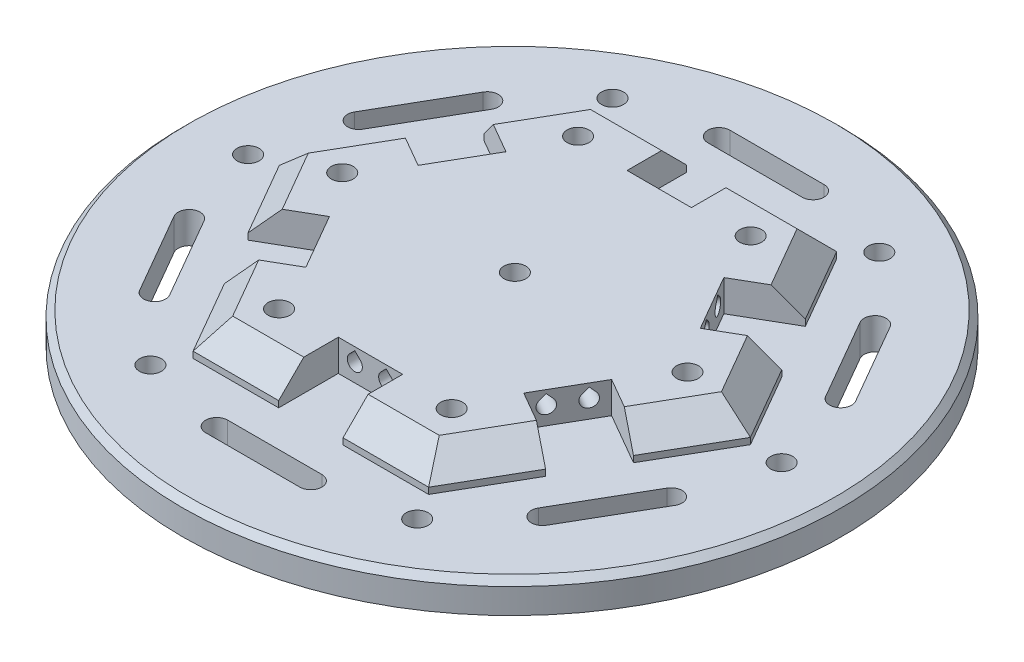
SolidWorks part; units mm, degrees
ref_plane "前基準面" through (0, 0, 0) normal (0, 0, 1) x (1, 0, 0)
ref_plane "上基準面" through (0, 0, 0) normal (0, 1, 0) x (1, 0, 0)
ref_plane "右基準面" through (0, 0, 0) normal (1, 0, 0) x (0, 0, -1)
sketch "草圖1" plane through (0, 0, 0) normal (0, 1, 0) x (1, 0, 0)
  line L0 (0, -1000) -> (0, 49000) construction
  line L1 (75.0555, 0) -> (37.5278, 65)
  line L2 (37.5278, 65) -> (-37.5278, 65)
  line L3 (-37.5278, 65) -> (-75.0555, 0)
  line L4 (-75.0555, 0) -> (-37.5278, -65)
  line L5 (-37.5278, -65) -> (37.5278, -65)
  line L6 (37.5278, -65) -> (75.0555, 0)
  line L7 (-10.25, 49) -> (10.25, 49)
  line L8 (-10.25, 49) -> (-10.25, 46)
  line L9 (-10.25, 46) -> (10.25, 46)
  line L10 (10.25, 49) -> (10.25, 46)
  line L11 (37.3102, 33.3768) -> (34.7122, 31.8768)
  line L12 (-10.25, 46) -> (10.25, 46) construction
  line L13 (-10.25, 46) -> (-10.25, 18) construction
  line L14 (-10.25, 18) -> (10.25, 18) construction
  line L15 (10.25, 46) -> (10.25, 18) construction
  line L16 (37.3102, 33.3768) -> (47.5602, 15.6232)
  line L17 (47.5602, 15.6232) -> (44.9622, 14.1232)
  line L18 (34.7122, 31.8768) -> (44.9622, 14.1232)
  line L19 (44.9622, 14.1232) -> (20.7135, 0.1232) construction
  line L20 (10.4635, 17.8768) -> (20.7135, 0.1232) construction
  line L21 (34.7122, 31.8768) -> (10.4635, 17.8768) construction
  line L22 (47.5602, -15.6232) -> (44.9622, -14.1232)
  line L23 (47.5602, -15.6232) -> (37.3102, -33.3768)
  line L24 (37.3102, -33.3768) -> (34.7122, -31.8768)
  line L25 (44.9622, -14.1232) -> (34.7122, -31.8768)
  line L26 (34.7122, -31.8768) -> (10.4635, -17.8768) construction
  line L27 (20.7135, -0.1232) -> (10.4635, -17.8768) construction
  line L28 (44.9622, -14.1232) -> (20.7135, -0.1232) construction
  line L29 (10.25, -49) -> (10.25, -46)
  line L30 (10.25, -49) -> (-10.25, -49)
  line L31 (-10.25, -49) -> (-10.25, -46)
  line L32 (10.25, -46) -> (-10.25, -46)
  line L33 (-10.25, -46) -> (-10.25, -18) construction
  line L34 (10.25, -18) -> (-10.25, -18) construction
  line L35 (10.25, -46) -> (10.25, -18) construction
  line L36 (-37.3102, -33.3768) -> (-34.7122, -31.8768)
  line L37 (-37.3102, -33.3768) -> (-47.5602, -15.6232)
  line L38 (-47.5602, -15.6232) -> (-44.9622, -14.1232)
  line L39 (-34.7122, -31.8768) -> (-44.9622, -14.1232)
  line L40 (-44.9622, -14.1232) -> (-20.7135, -0.1232) construction
  line L41 (-10.4635, -17.8768) -> (-20.7135, -0.1232) construction
  line L42 (-34.7122, -31.8768) -> (-10.4635, -17.8768) construction
  line L43 (-47.5602, 15.6232) -> (-44.9622, 14.1232)
  line L44 (-47.5602, 15.6232) -> (-37.3102, 33.3768)
  line L45 (-37.3102, 33.3768) -> (-34.7122, 31.8768)
  line L46 (-44.9622, 14.1232) -> (-34.7122, 31.8768)
  line L47 (-34.7122, 31.8768) -> (-10.4635, 17.8768) construction
  line L48 (-20.7135, 0.1232) -> (-10.4635, 17.8768) construction
  line L49 (-44.9622, 14.1232) -> (-20.7135, 0.1232) construction
  line L51 (10.25, 46) -> (-10.25, 46)
  line L52 (10.25, 46) -> (10.25, 65)
  line L53 (10.25, 65) -> (-10.25, 65)
  line L54 (-10.25, 46) -> (-10.25, 65)
  circle A0 centre (0, 0) radius 65 construction
  circle A2 centre (0, 0) radius 46 construction
  point P14 (0, 46)
  point P51 (0, 0)
  dimension "D1" = 130
  dimension "D2" = 16
  dimension "D3" = 20.5
  dimension "D4" = 3
  dimension "D5" = 28
  dimension "D6" = 6
extrude "填料-伸長1" add sketch "草圖1" along normal blind 10 contours L8 L54 L2 L3 L4 L5 L6 L1 L52 L10 L9 L46 L43 L44 L45 L39 L36 L37 L38 L32 L29 L30 L31 L25 L22 L23 L24 L18 L11 L16 L17 | L54 L7 L52 L2 | L11 L18 L17 L16 | L22 L25 L24 L23 | L36 L39 L38 L37 | L43 L46 L45 L44 | L10 L7 L8 L9 | L29 L32 L31 L30 region at (0, 0, 1.3413) region at (0, 0, -57) region at (0, 0, -47.5) region at (41.1362, 0, -23.75) region at (41.1362, 0, 23.75) region at (0, 0, 47.5) region at (-41.1362, 0, 23.75) region at (-41.1362, 0, -23.75)
chamfer "導角1" distance 8 angle 45 6 edges at (56.2917, 10, 32.5) (0, 10, 65) (-56.2917, 10, 32.5) (-56.2917, 10, -32.5) (0, 10, -65) (56.2917, 10, -32.5)
extrude "除料-伸長2" cut sketch "草圖1<3>" along normal blind 10 contours L54 L7 L52 L2 | L10 L7 L8 L9 region at (0, 0, -57) region at (0, 0, -47.5)
sketch "草圖1<3>" plane through (0, 0, 0) normal (0, 1, 0) x (1, 0, 0) same geometry as "草圖1"
ref_axis "基準軸1" through (0, 10.5, 0) along (0, -1, 0)
sketch "草圖2" plane through (0, 0, -46) normal (0, 0, -1) x (-1, 0, 0)
  line L0 (10.25, 10) -> (-10.25, 10) construction
  line L2 (-5, 5.5) -> (5, 5.5) construction
  line L3 (0, 10.5) -> (0, -0.5) construction
  line L4 (5, -994.5) -> (5, 49005.5) construction
  line L5 (-5, -994.5) -> (-5, 49005.5) construction
  line L6 (-6.6971, 7.1971) -> (-5, 8.8941)
  line L7 (-5, 8.8941) -> (-3.3029, 7.1971)
  line L8 (3.3029, 7.1971) -> (5, 8.8941)
  line L9 (5, 8.8941) -> (6.6971, 7.1971)
  arc A0 (-6.6971, 7.1971) -> (-3.3029, 7.1971) centre (-5, 5.5) ccw
  arc A1 (3.3029, 7.1971) -> (6.6971, 7.1971) centre (5, 5.5) ccw
  point P6 (0, 5.5)
  dimension "D1" = 4.8
  dimension "D2" = 4.8
  dimension "D3" = 4.5
  dimension "D4" = 4.5
  dimension "D5" = 10
  dimension "D6" = 90
  dimension "D7" = 90
extrude "除料-伸長3" cut sketch "草圖2" against normal blind 8.5
sketch "草圖6" plane through (0, 10, 0) normal (0, 1, 0) x (1, 0, 0)
  line L0 (-15.25, 61) -> (-10.25, 54.3333)
  line L2 (-10.25, 46) -> (-10.25, 18)
  line L3 (-10.25, 18) -> (10.25, 18)
  line L4 (10.25, 18.6667) -> (10.25, 18)
  line L5 (15.25, 20.3333) -> (15.25, 13)
  line L6 (-15.25, 13) -> (15.25, 13)
  line L7 (-15.25, 61) -> (-15.25, 13)
  line L8 (-10.25, 46) -> (-10.25, 54.3333)
  line L9 (-10.25, 46) -> (-10.25, 57) construction
  line L10 (10.25, 18.6667) -> (-3.3654, 45.1538)
  line L13 (-3.3654, 45.1538) -> (15.25, 20.3333)
  line L14 (-10.25, 46) -> (10.25, 18.6667) construction
  line L15 (-15.25, 61) -> (15.25, 20.3333) construction
  dimension "D1" = 28
  dimension "D2" = 20.5
  dimension "D3" = 5
extrude "填料-伸長2" [suppressed] add sketch "草圖6" along normal blind 10
pattern_circular "環狀複製排列1" count 6 over 360 about axis through (0, 10.5, 0) along (0, -1, 0) of "除料-伸長2", "除料-伸長3"
sketch "草圖11" plane through (0, 10, 0) normal (0, 1, 0) x (1, 0, 0)
  line L0 (-61.4167, 23.6232) -> (-75.0555, 0) construction
  line L1 (-68.2361, 11.8116) -> (-98.2361, 11.8116)
  line L2 (-68.2361, 11.8116) -> (-68.2361, -11.8116)
  line L3 (-68.2361, -11.8116) -> (-98.2361, -11.8116)
  line L4 (-98.2361, 11.8116) -> (-98.2361, -11.8116)
  line L5 (-75.0555, 0) -> (-61.4167, -23.6232) construction
  circle A0 centre (0, 0) radius 100
  point P9 (0, 0)
  dimension "D2" = 200
  dimension "D1" = 30
extrude "填料-伸長4" [suppressed] add sketch "草圖11" against normal blind 10 contours L2 L1 L4 L3
fillet "圓角1" [suppressed] radius 10
sketch "草圖9" plane through (0, 0, 0) normal (0, -1, 0) x (1, 0, 0)
  circle A0 centre (0, 0.9115) radius 105
  dimension "D1" = 210
extrude "填料-伸長3" add sketch "草圖9" along normal blind 10
sketch "草圖7" plane through (0, 10, 0) normal (0, 1, 0) x (1, 0, 0)
  circle A0 centre (0, 0) radius 3.5
  dimension "D1" = 7
extrude "除料-伸長4" cut sketch "草圖7" against normal through all
sketch "草圖10" plane through (0, 0, 0) normal (0, 1, 0) x (1, 0, 0)
  line L0 (-15, 80) -> (15, 80) construction
  line L1 (-15, 83.5) -> (15, 83.5)
  line L2 (-15, 76.5) -> (15, 76.5)
  arc A1 (-15, 83.5) -> (-15, 76.5) centre (-15, 80) ccw
  arc A2 (15, 76.5) -> (15, 83.5) centre (15, 80) ccw
  point P2 (0, 80)
  point P8 (0, 0)
  dimension "D1" = 7
  dimension "D2" = 30
  dimension "D3" = 80
extrude "除料-伸長5" cut sketch "草圖10" against normal through all
pattern_circular "環狀複製排列2" count 6 over 360 about axis through (0, 10.5, 0) along (0, -1, 0) of "除料-伸長5"
chamfer "導角2" distance 2 angle 45 1 edges at (0, 0, -104.0885)
sketch "草圖13" plane through (0, 10, 0) normal (0, 1, 0) x (1, 0, 0)
  line L0 (0, 0) -> (52.1048, 90.2482)
  line L1 (0, 0) -> (104.996, 0)
  circle A0 centre (27.5, 47.6314) radius 3.5
  circle A1 centre (0, -0.9115) radius 105 construction
  circle A2 centre (42.5, 73.6122) radius 3.5
  dimension "D3" = 7
  dimension "D4" = 7
  dimension "D1" = 55
  dimension "D2" = 60
  dimension "D5" = 85
extrude "除料-伸長6" cut sketch "草圖13" against normal through all contours A0 | A2
pattern_circular "環狀複製排列3" count 6 over 360 about axis through (0, 10.5, 0) along (0, -1, 0) of "除料-伸長6"
sketch "草圖15" plane through (0, -10, 0) normal (0, -1, 0) x (1, 0, 0)
  line L0 (-32.695, -40.6585) -> (26.7489, -40.6585) construction
  text T0 "D" font "CommercialScript BT" height 30
  point P3 (146.3308, -38.25)
  point P4 (118.2199, -39.2841)
  point P5 (105.6135, -38.7045)
  point P6 (101.4114, -39.2841)
  point P7 (95.9051, -39.5739)
  point P8 (-62.996, -23.4876)
  point P9 (73.5128, -23.5096)
  point P10 (-29.342, -30.6391)
  point P11 (20.0872, -30.6391)
  point P12 (26.7489, -41.0021)
  point P13 (-32.695, -40.6585)
extrude "除料-伸長7" cut sketch "草圖15" against normal blind 0.6
